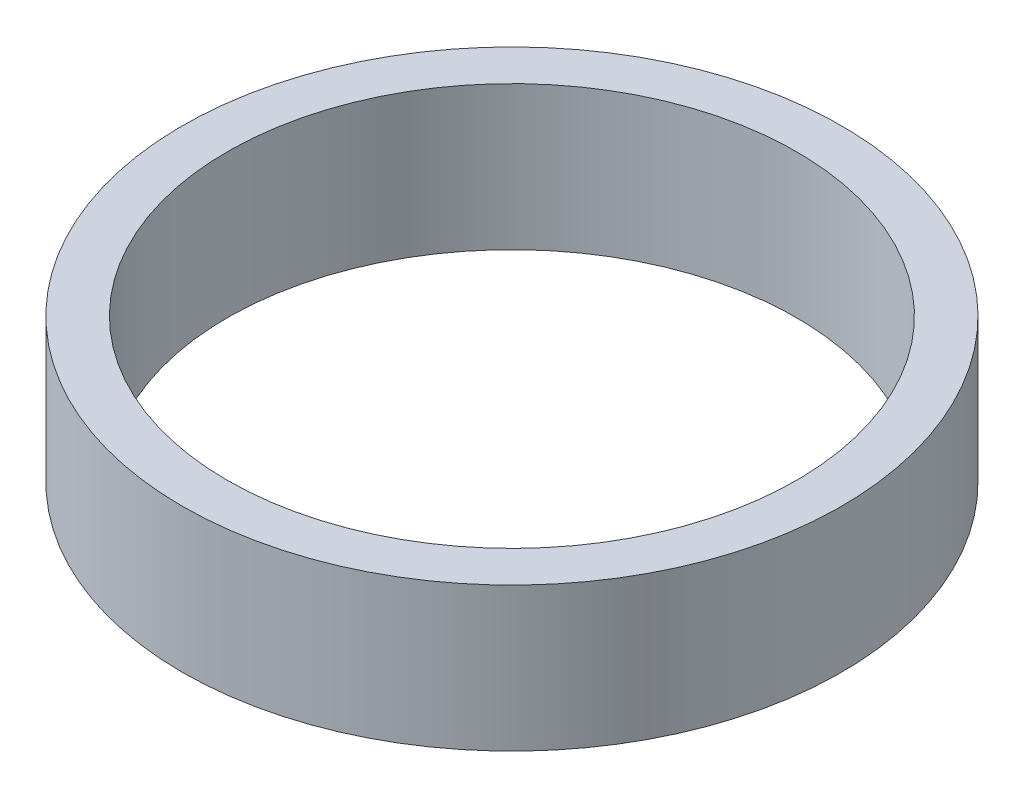
SolidWorks part; units mm, degrees
ref_plane "Front Plane" through (0, 0, 0) normal (0, 0, 1) x (1, 0, 0)
ref_plane "Top Plane" through (0, 0, 0) normal (0, 1, 0) x (1, 0, 0)
ref_plane "Right Plane" through (0, 0, 0) normal (1, 0, 0) x (0, 0, -1)
sketch "Sketch1" plane through (0, 0, 0) normal (0, 1, 0) x (1, 0, 0)
  circle A0 centre (0, 0) radius 55
  dimension "FLANGE_OD" = 110
extrude "Boss-Extrude1" add sketch "Sketch1" along normal blind 24
sketch "Sketch2" plane through (0, 0, 0) normal (0, 1, 0) x (1, 0, 0)
  circle A0 centre (0, 0) radius 47.5
  dimension "BORE_D" = 95
extrude "Cut-Extrude1" cut sketch "Sketch2" along normal through all
sketch "Sketch3" plane through (0, 24, 0) normal (0, 1, 0) x (1, 0, 0)
  circle A0 centre (0, 0) radius 25.4709 construction
  circle A1 centre (-25.4709, 0) radius 1.5
  dimension "BOLT_D" = 3
  dimension "BOLT_PCD" = 50.9418
extrude "Cut-Extrude2" cut sketch "Sketch3" against normal blind 22.6958 rebuild error yes
pattern_circular "CirPattern1" count 5 over 360 rebuild error yes
